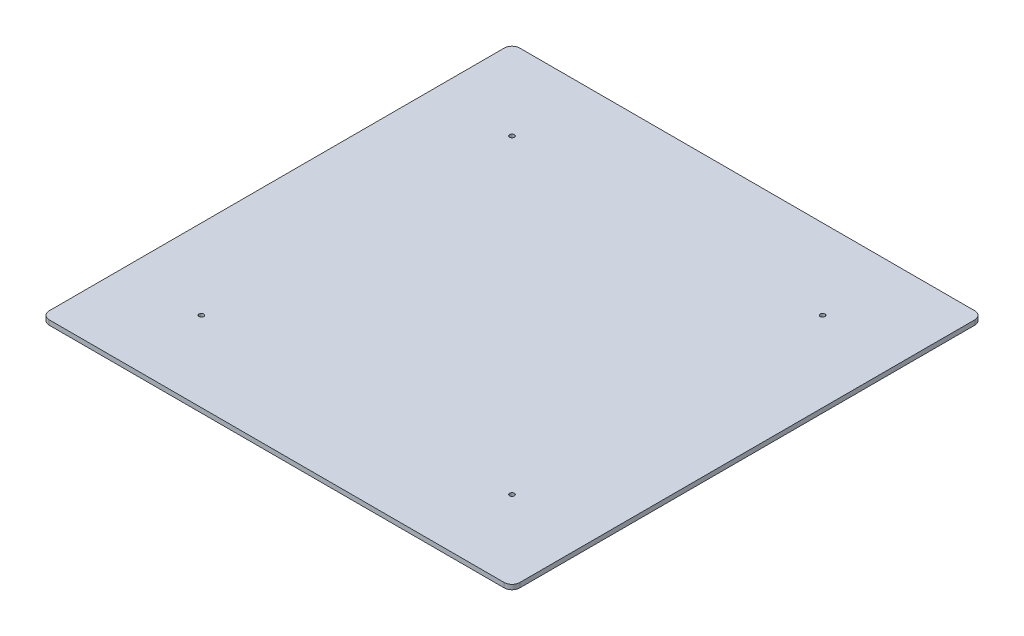
SolidWorks part; units mm, degrees
ref_plane "Front Plane" through (0, 0, 0) normal (0, 0, 1) x (1, 0, 0)
ref_plane "Top Plane" through (0, 0, 0) normal (0, 1, 0) x (1, 0, 0)
ref_plane "Right Plane" through (0, 0, 0) normal (1, 0, 0) x (0, 0, -1)
sketch "Sketch1" plane through (0, 0, 0) normal (0, 1, 0) x (1, 0, 0)
  line L0 (-150, -150) -> (150, 150) construction
  line L1 (-150, 150) -> (150, 150)
  line L2 (-150, 150) -> (-150, -150)
  line L3 (-150, -150) -> (150, -150)
  line L4 (150, 150) -> (150, -150)
  line L5 (-150, 150) -> (150, -150) construction
  circle A0 centre (-98.9949, -98.9949) radius 1.5
  circle A1 centre (-98.9949, 98.9949) radius 1.5
  circle A2 centre (98.9949, 98.9949) radius 1.5
  circle A3 centre (98.9949, -98.9949) radius 1.5
  point P4 (0, 0)
  point P17 (0, 0)
  dimension "D3" = 3
  dimension "D6" = 140
  dimension "D1" = 300
  dimension "D2" = 300
  dimension "D4" = 140
  dimension "D5" = 4
extrude "Boss-Extrude1" add sketch "Sketch1" along normal blind 3
fillet "Fillet1" radius 5 4 edges at (150, 1.5, 150) (150, 1.5, -150) (-150, 1.5, -150) (-150, 1.5, 150)
